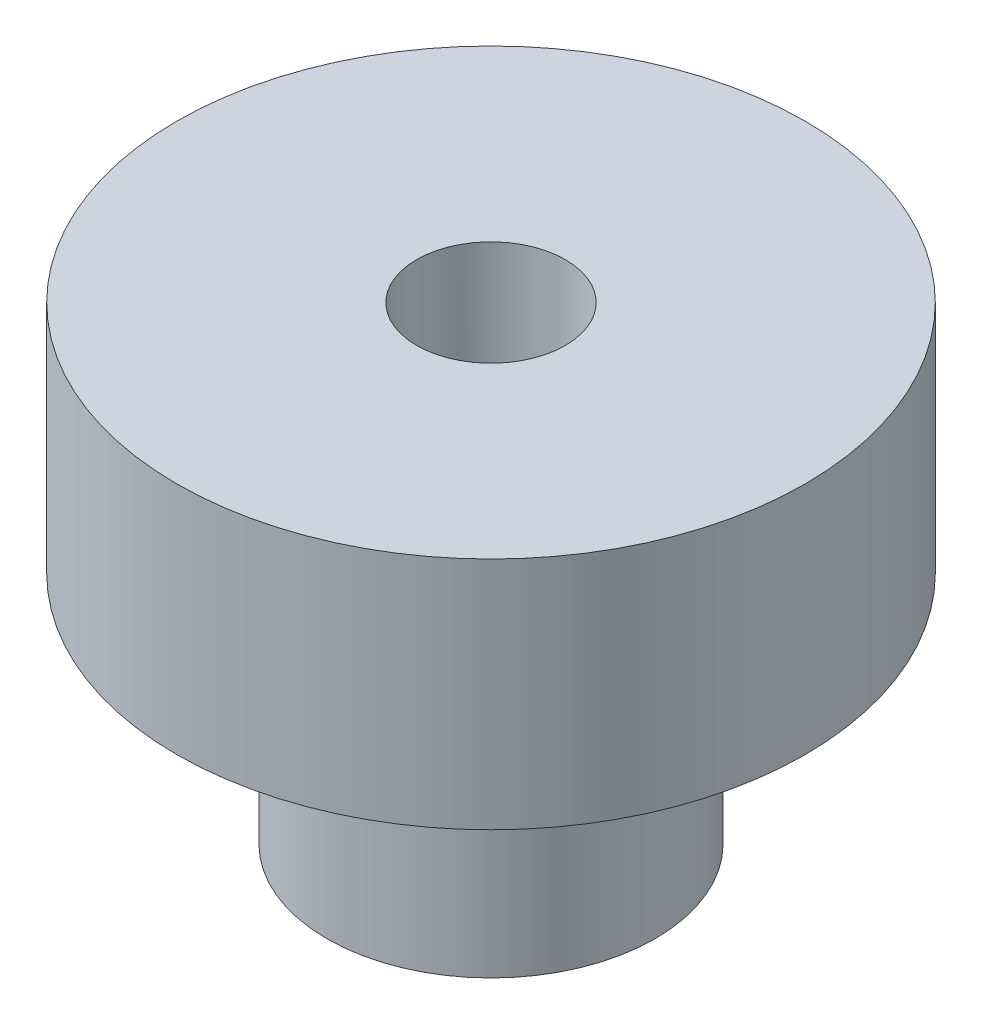
SolidWorks part; units mm, degrees
ref_plane "Front Plane" through (0, 0, 0) normal (0, 0, 1) x (1, 0, 0)
ref_plane "Top Plane" through (0, 0, 0) normal (0, 1, 0) x (1, 0, 0)
ref_plane "Right Plane" through (0, 0, 0) normal (1, 0, 0) x (0, 0, -1)
sketch "Sketch1" plane through (0, 0, 0) normal (0, 1, 0) x (1, 0, 0)
  circle A0 centre (0, 0) radius 6.7
  circle A1 centre (0, 0) radius 1.586
  dimension "D1" = 13.4
  dimension "D2" = 3.172
extrude "Boss-Extrude1" add sketch "Sketch1" along normal blind 5
sketch "Sketch2" plane through (0, 0, 0) normal (0, -1, 0) x (1, 0, 0)
  circle A0 centre (0, 0) radius 3.5
  circle A1 centre (0, 0) radius 1.586
  circle A2 centre (0, 0) radius 1.586 construction
  dimension "D1" = 7
extrude "Boss-Extrude2" add sketch "Sketch2" along normal blind 5
sketch "Sketch3" plane through (0, 0, 0) normal (1, 0, 0) x (0, 0, -1)
  line L0 (0, 0) -> (0, -5) construction
  line L1 (-3.5, -5) -> (3.5, -5) construction
  line L2 (-3.5, -2.5) -> (3.5, -2.5) construction
  line L3 (3.5, -5) -> (3.5, 0) construction
  circle A0 centre (0, -2.5) radius 1.25
  point P10 (0, -2.5)
  dimension "D1" = 2.5
extrude "Cut-Extrude1" cut sketch "Sketch3" against normal blind 10
